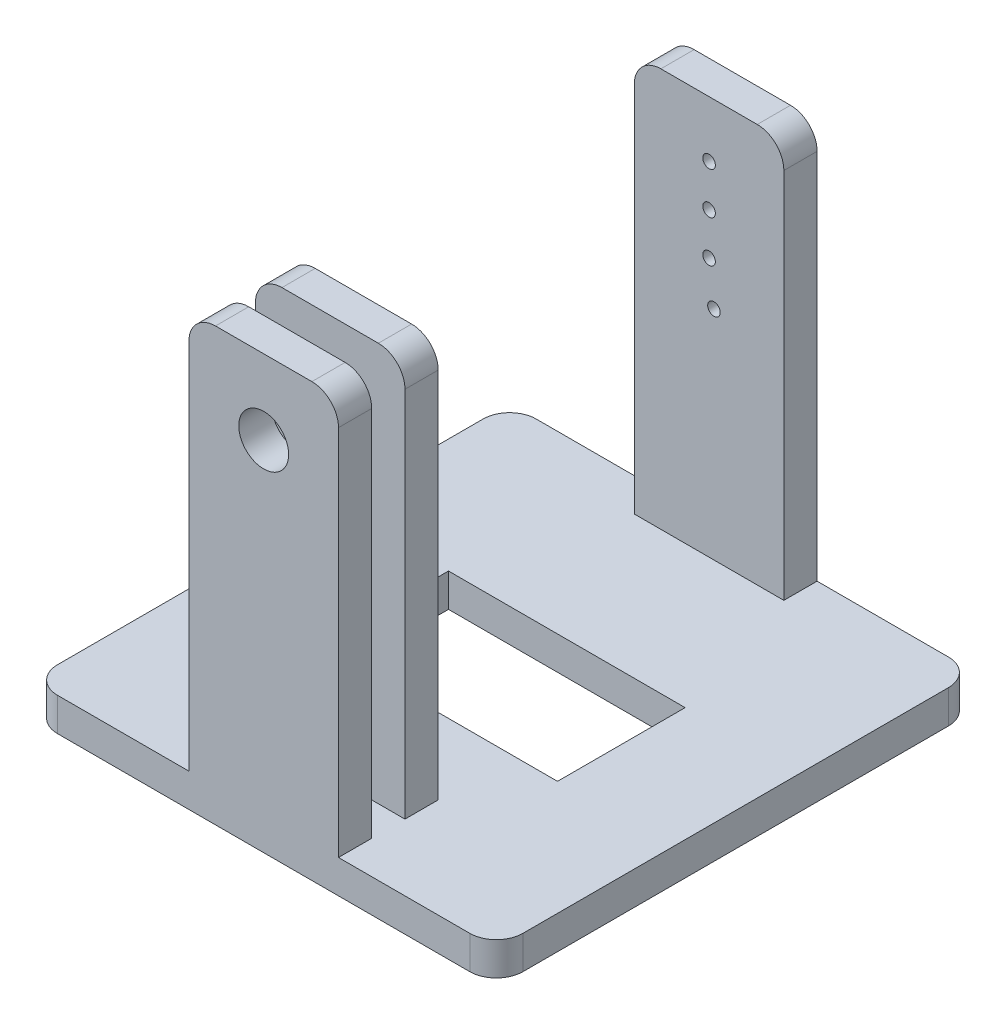
SolidWorks part; units mm, degrees
material "6061 Alloy"
ref_plane "Front Plane" through (0, 0, 0) normal (0, 0, 1) x (1, 0, 0)
ref_plane "Top Plane" through (0, 0, 0) normal (0, 1, 0) x (1, 0, 0)
ref_plane "Right Plane" through (0, 0, 0) normal (1, 0, 0) x (0, 0, -1)
sketch "Sketch1" plane through (0, 0, 0) normal (0, 1, 0) x (1, 0, 0)
  line L0 (19.7243, -19.7321) -> (19.7243, 25.9879)
  line L1 (19.7243, 25.9879) -> (-24.7257, 25.9879)
  line L2 (-24.7257, 25.9879) -> (-24.7257, -19.7321)
  line L3 (-24.7257, -19.7321) -> (19.7243, -19.7321)
  line L5 (-13.8037, -2.9681) -> (8.8023, -2.9681)
  line L6 (-13.8037, -2.9681) -> (-13.8037, 9.2239)
  line L7 (-13.8037, 9.2239) -> (8.8023, 9.2239)
  line L8 (8.8023, -2.9681) -> (8.8023, 9.2239)
  line L9 (-13.8037, -2.9681) -> (8.8023, 9.2239) construction
  line L10 (-13.8037, 9.2239) -> (8.8023, -2.9681) construction
  point P0 (8.8023, 3.1279)
  point P1 (19.7243, 3.1279)
  point P2 (-2.5007, -2.9681)
  point P3 (-2.5007, -19.7321)
  point P14 (-2.5007, 9.2239)
  point P15 (-2.5007, 25.9879)
  dimension "D1" = 22.606
  dimension "D2" = 12.192
  dimension "D3" = 45.72
  dimension "D4" = 44.45
extrude "Boss-Extrude1" add sketch "Sketch1" along normal blind 3.175
sketch "Sketch4" plane through (0, 3.175, 0) normal (0, 1, 0) x (1, 0, 0)
  line L0 (-24.7257, 3.1279) -> (19.7243, 3.1279) construction
  line L1 (-24.7257, 25.9879) -> (-24.7257, -19.7321) construction
  line L2 (19.7243, -19.7321) -> (19.7243, 25.9879) construction
  line L3 (-2.5007, 25.9879) -> (-2.5007, -23.8438) construction
  line L4 (19.7243, 25.9879) -> (-24.7257, 25.9879) construction
  point P10 (0, 0)
  point P12 (-0.3299, -23.8438)
sketch "Sketch5" plane through (0, 0, 0) normal (1, 0, 0) x (0, 0, -1)
  line L0 (-19.7321, 3.175) -> (-19.7321, 41.275)
  line L1 (-19.7321, 41.275) -> (-16.5571, 41.275)
  line L2 (-16.5571, 41.275) -> (-16.5571, 3.175)
  line L3 (25.9879, 3.175) -> (25.9879, 41.275)
  line L4 (-16.5571, 3.175) -> (-19.7321, 3.175)
  line L5 (-13.3821, 3.175) -> (-13.3821, 41.275)
  line L6 (-13.3821, 41.275) -> (-10.2071, 41.275)
  line L7 (-10.2071, 41.275) -> (-10.2071, 3.175)
  line L8 (-13.3821, 3.175) -> (-10.2071, 3.175)
  line L9 (-19.7321, 3.175) -> (25.9879, 3.175) construction
  line L10 (25.9879, 41.275) -> (22.8129, 41.275)
  line L11 (-19.7321, 3.175) -> (-19.7321, 0) construction
  line L12 (22.8129, 41.275) -> (22.8129, 3.175)
  line L13 (25.9879, 3.175) -> (-23.8438, 3.175) construction
  line L14 (22.8129, 3.175) -> (25.9879, 3.175)
  point P19 (0, 0)
  dimension "D1" = 38.1
  dimension "D2" = 38.1
  dimension "D3" = 3.175
  dimension "D4" = 3.175
  dimension "D5" = 3.175
  dimension "D6" = 3.175
extrude "Boss-Extrude2" add sketch "Sketch5" along normal mid plane 14.2875 from vertex starting at point (-2.5007, 3.175, 23.8438)
sketch "Sketch6" plane through (0, 0, 19.7321) normal (0, 0, 1) x (1, 0, 0)
  line L0 (-2.5007, 41.275) -> (-2.5007, 31.75) construction
  line L1 (4.6431, 41.275) -> (-9.6444, 41.275) construction
  circle A0 centre (-2.5007, 34.1312) radius 2.3813
  point P8 (-2.5007, 36.5125)
  dimension "D2" = 4.7625
  dimension "D1" = 4.7625
extrude "Cut-Extrude2" cut sketch "Sketch6" against normal up to surface (9.525 mm away) up to face at (-2.5007, 22.225, 10.2071)
fillet "Fillet1" radius 2.54 10 edges at (19.7243, 1.5875, 19.7321) (19.7243, 1.5875, -25.9879) (-24.7257, 1.5875, 19.7321) (-24.7257, 1.5875, -25.9879) (-9.6444, 41.275, 18.1446) (-9.6444, 41.275, 11.7946) (4.6431, 41.275, 11.7946) (4.6431, 41.275, 18.1446) (-9.6444, 41.275, -24.4004) (4.6431, 41.275, -24.4004)
sketch "Sketch2" plane through (0, 0, -25.9879) normal (0, 0, -1) x (-1, 0, 0)
  line L0 (2.5007, 0) -> (2.5007, 3.175)
  line L1 (-17.1843, 0) -> (22.1857, 0) construction
  line L2 (-19.7243, 3.175) -> (24.7257, 3.175) construction
sketch "Sketch7" plane through (0, 0, -25.9879) normal (0, 0, -1) x (-1, 0, 0)
  line L3 (2.5007, 41.275) -> (2.5007, 3.175) construction
  line L4 (-2.1031, 41.275) -> (7.1044, 41.275) construction
  line L5 (-17.1843, 3.175) -> (-4.6431, 3.175) construction
  circle A2 centre (2.0333, 23.9399) radius 0.6
  circle A3 centre (2.5007, 27.9125) radius 0.6
  circle A4 centre (2.5007, 31.9125) radius 0.6
  circle A5 centre (2.5007, 35.9125) radius 0.6
  point P0 (2.5007, 36.5125)
  dimension "D5" = 1.2
  dimension "D1" = 4.7625
  dimension "D2" = 4
  dimension "D3" = 4
  dimension "D4" = 4
extrude "Cut-Extrude3" cut sketch "Sketch7" against normal up to next
